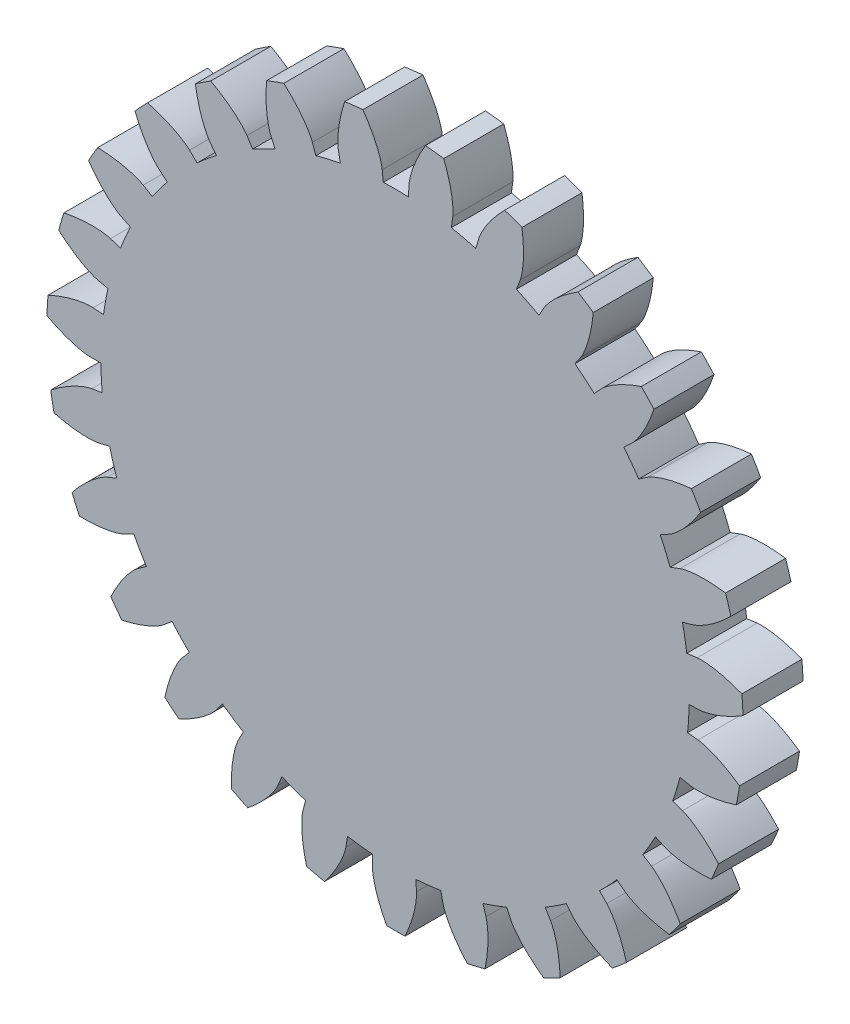
SolidWorks part; units mm, degrees
ref_plane "Спереди" through (0, 0, 0) normal (0, 0, 1) x (1, 0, 0)
ref_plane "Сверху" through (0, 0, 0) normal (0, 1, 0) x (1, 0, 0)
ref_plane "Справа" through (0, 0, 0) normal (1, 0, 0) x (0, 0, -1)
sketch "Эскиз2" plane through (0, 0, 0) normal (0, 0, 1) x (1, 0, 0)
  line L0 (0, 51.1792) -> (0, -43.95) construction
  line L1 (10.2103, 50.2838) -> (97.1798, 18.6294) construction
  line L2 (-13.5021, 54) -> (13.4511, 54) construction
  line L3 (2.3205, 50.6903) -> (2.2389, 48.9488)
  line L6 (-2.1304, 50.6987) -> (-1.9549, 48.961)
  circle A0 centre (0, 0) radius 58
  circle A1 centre (0, 0) radius 54 construction
  circle A2 centre (0, 0) radius 50.7434 construction
  circle A3 centre (0, 0) radius 49
  spline S0 degree 4 poles (2.3205, 50.6903) (2.3244, 50.7735) (2.3371, 50.9394) (2.3792, 51.2535) (2.4646, 51.7126) (2.6518, 52.4976) (3.0384, 53.7202) (3.6973, 55.3169) (4.8184, 57.4548) (6.365, 59.823) (8.2953, 62.2583) (10.599, 64.6898) (13.0865, 66.9317) (15.7286, 68.9884) (18.6386, 70.9572) (22.3961, 73.1503) (27.0782, 75.3922) (32.7364, 77.4792) (39.2217, 79.1667) (45.8331, 80.2522) (51.6775, 80.7005) (56.6988, 80.7439) (60.8778, 80.5616) (64.2131, 80.2879) (68.3661, 79.7902) (72.4916, 79.0902) (76.5784, 78.1965) (81.4284, 76.8999) (85.0169, 75.7655) (88.1696, 74.6336) (90.8878, 73.5583) (92.2483, 72.9942) (93.3842, 72.5067) (94.4257, 72.045) (95.2299, 71.6826) (96.3696, 71.152) (97.2139, 70.749) (98.5986, 70.0721) (99.653, 69.533) (100.9412, 68.8642) (102.0722, 68.252) (103.2922, 67.5792) (104.2914, 67.0073) (105.184, 66.4886) (105.7538, 66.149) (106.0474, 65.9735) (106.1916, 65.8866) knots 0 0 0 0 0 0.002802 0.005604 0.010661 0.015718 0.02996 0.048734 0.068727 0.096889 0.125051 0.153212 0.181374 0.209535 0.237696 0.271429 0.327752 0.384075 0.440398 0.496721 0.553044 0.581206 0.609367 0.637529 0.66569 0.722013 0.750174 0.778336 0.834659 0.84874 0.86282 0.876901 0.883942 0.890982 0.900036 0.909091 0.920455 0.931818 0.943182 0.954545 0.965909 0.977273 0.988636 0.994318 1 1 1 1 1 construction
  spline S1 degree 4 poles (2.3205, 50.6903) (2.3244, 50.7735) (2.3371, 50.9394) (2.3792, 51.2535) (2.4646, 51.7126) (2.6518, 52.4976) (3.0384, 53.7202) (3.6973, 55.3169) (4.8184, 57.4548) (6.365, 59.823) (8.2953, 62.2583) (10.599, 64.6898) (13.0865, 66.9317) (15.7286, 68.9884) (18.6386, 70.9572) (22.3961, 73.1503) (27.0782, 75.3922) (32.7364, 77.4792) (39.2217, 79.1667) (45.8331, 80.2522) (51.6775, 80.7005) (56.6988, 80.7439) (60.8778, 80.5616) (64.2131, 80.2879) (68.3661, 79.7902) (72.4916, 79.0902) (76.5784, 78.1965) (81.4284, 76.8999) (85.0169, 75.7655) (88.1696, 74.6336) (90.8878, 73.5583) (92.2483, 72.9942) (93.3842, 72.5067) (94.4257, 72.045) (95.2299, 71.6826) (96.0149, 71.3171) (96.4629, 71.1059) (96.6836, 71.0008) knots 0 0 0 0 0 0.002802 0.005604 0.010661 0.015718 0.02996 0.048734 0.068727 0.096889 0.125051 0.153212 0.181374 0.209535 0.237696 0.271429 0.327752 0.384075 0.440398 0.496721 0.553044 0.581206 0.609367 0.637529 0.66569 0.722013 0.750174 0.778336 0.834659 0.84874 0.86282 0.876901 0.883942 0.890982 0.900036 0.909091 0.909091 0.909091 0.909091 0.909091
  spline S2 degree 4 poles (-2.1304, 50.6987) (-2.1388, 50.7815) (-2.1605, 50.9465) (-2.2194, 51.2579) (-2.3294, 51.7117) (-2.5585, 52.4855) (-3.0103, 53.6856) (-3.7541, 55.2445) (-4.9887, 57.319) (-6.6604, 59.6006) (-8.7189, 61.9285) (-11.15, 64.2325) (-13.7545, 66.3374) (-16.5034, 68.249) (-19.5152, 70.0584) (-23.3852, 72.0462) (-28.181, 74.033) (-33.9433, 75.8126) (-40.51, 77.1489) (-47.1703, 77.8771) (-53.0303, 78.0103) (-58.0467, 77.7837) (-62.2098, 77.3768) (-65.5255, 76.924) (-69.6458, 76.2037) (-73.7277, 75.2827) (-77.7604, 74.1706) (-82.5336, 72.6149) (-86.056, 71.2891) (-89.1432, 69.9893) (-91.7996, 68.7693) (-93.1278, 68.1329) (-94.2359, 67.585) (-95.251, 67.0679) (-96.0346, 66.6627) (-97.1441, 66.0717) (-97.9655, 65.6238) (-99.3118, 64.8734) (-100.3356, 64.2784) (-101.5859, 63.5413) (-102.6824, 62.8691) (-103.8644, 62.1316) (-104.8314, 61.5068) (-105.6948, 60.9409) (-106.2455, 60.5711) (-106.5293, 60.3801) (-106.6686, 60.2856) knots 0 0 0 0 0 0.002802 0.005604 0.010661 0.015718 0.02996 0.048734 0.068727 0.096889 0.125051 0.153212 0.181374 0.209535 0.237696 0.271429 0.327752 0.384075 0.440398 0.496721 0.553044 0.581206 0.609367 0.637529 0.66569 0.722013 0.750174 0.778336 0.834659 0.84874 0.86282 0.876901 0.883942 0.890982 0.900036 0.909091 0.920455 0.931818 0.943182 0.954545 0.965909 0.977273 0.988636 0.994318 1 1 1 1 1 construction
  spline S3 degree 4 poles (-2.1304, 50.6987) (-2.1388, 50.7815) (-2.1605, 50.9465) (-2.2194, 51.2579) (-2.3294, 51.7117) (-2.5585, 52.4855) (-3.0103, 53.6856) (-3.7541, 55.2445) (-4.9887, 57.319) (-6.6604, 59.6006) (-8.7189, 61.9285) (-11.15, 64.2325) (-13.7545, 66.3374) (-16.5034, 68.249) (-19.5152, 70.0584) (-23.3852, 72.0462) (-28.181, 74.033) (-33.9433, 75.8126) (-40.51, 77.1489) (-47.1703, 77.8771) (-53.0303, 78.0103) (-58.0467, 77.7837) (-62.2098, 77.3768) (-65.5255, 76.924) (-69.6458, 76.2037) (-73.7277, 75.2827) (-77.7604, 74.1706) (-82.5336, 72.6149) (-86.056, 71.2891) (-89.1432, 69.9893) (-91.7996, 68.7693) (-93.1278, 68.1329) (-94.2359, 67.585) (-95.251, 67.0679) (-96.0346, 66.6627) (-96.7988, 66.2556) (-97.2348, 66.0205) (-97.4495, 65.9037) knots 0 0 0 0 0 0.002802 0.005604 0.010661 0.015718 0.02996 0.048734 0.068727 0.096889 0.125051 0.153212 0.181374 0.209535 0.237696 0.271429 0.327752 0.384075 0.440398 0.496721 0.553044 0.581206 0.609367 0.637529 0.66569 0.722013 0.750174 0.778336 0.834659 0.84874 0.86282 0.876901 0.883942 0.890982 0.900036 0.909091 0.909091 0.909091 0.909091 0.909091
  point P9 (3.1401, 53.9086)
  point P18 (-3.1401, 53.9086)
  point P22 (0, 54)
  dimension "D1" = 116
  dimension "D2" = 108
  dimension "D4" = 98
  dimension "D5" = 20
  dimension "D6" = 3.1401
  dimension "D7" = 3.1401
extrude "Бобышка-Вытянуть1" add sketch "Эскиз2" along normal blind 10 contours A0
extrude "Вырез-Вытянуть1" cut sketch "Эскиз2<6>" along normal through all contours S3 L6 A3 L3 S1 A0 region at (-0.0124, 54.2098, 0)
sketch "Эскиз2<6>" plane through (0, 0, 0) normal (0, 0, 1) x (1, 0, 0) same geometry as "Эскиз2"
pattern_circular "Круговой массив2" count 27 over 360 about axis through (0, 0, 10) along (0, 0, -1) of "Вырез-Вытянуть1"
equation "\"Модуль\" = 4мм"
equation "\"Число зубьев\" = 27"
equation "\"Диаметр делительной окружности\"= \"Модуль\" * \"Число зубьев\""
equation "\"Диаметр вершин\"= \"Модуль\" * ( \"Число зубьев\" + 2 )"
equation "\"Диаметр впадин\"= \"Модуль\" * ( \"Число зубьев\" - 2.5 )"
equation "\"Угол давления\"= 20градусов"
equation "\"Угол наклона\"= 0градусов"
equation "\"Диаметр основной окружности\" = \"Диаметр делительной окружности\" * cos ( \"Угол давления\" )"
equation "\"Смещение\"= 0"
equation "\"Зазор\"= \"Модуль\" * 0.1"
equation "\"Толщина зуба по хорде делительной окружности\"= \"Диаметр делительной окружности\" * sin ( \"Модуль\" * pi * 57.3 / ( 2 * \"Диаметр делительной окружности\" ) )"
equation "\"D1@Эскиз2\"=\"Диаметр вершин\""
equation "\"D2@Эскиз2\"=\"Диаметр делительной окружности\""
equation "\"D4@Эскиз2\"=\"Диаметр впадин\""
equation "\"D5@Эскиз2\"=\"Угол давления\""
equation "\"D6@Эскиз2\" = \"Толщина зуба по хорде делительной окружности\" / 2"
equation "\"D7@Эскиз2\" = \"Толщина зуба по хорде делительной окружности\" / 2"
equation "\"D1@Круговой массив2\"=\"Число зубьев\""
